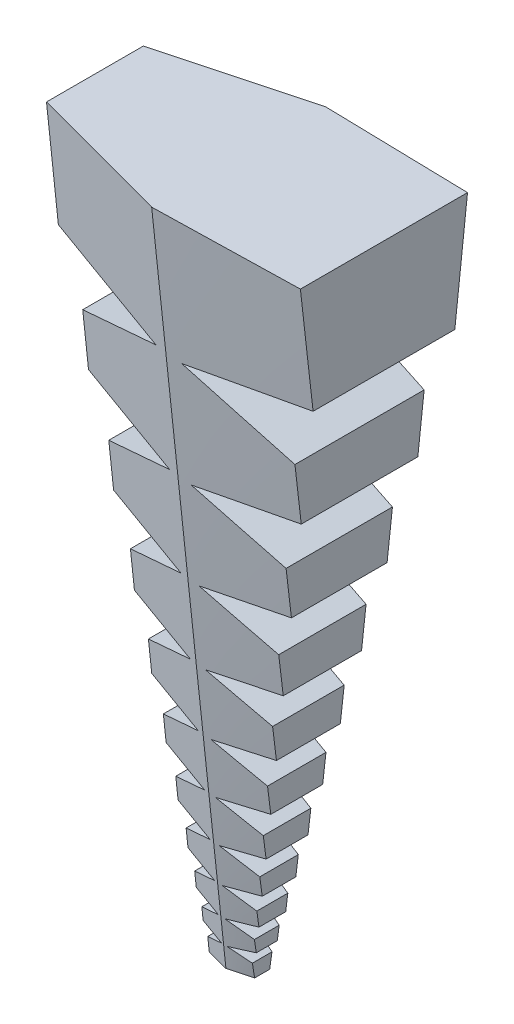
SolidWorks part; units mm, degrees
ref_plane "Front Plane" through (0, 0, 0) normal (0, 0, 1) x (1, 0, 0)
ref_plane "Top Plane" through (0, 0, 0) normal (0, 1, 0) x (1, 0, 0)
ref_plane "Right Plane" through (0, 0, 0) normal (1, 0, 0) x (0, 0, -1)
sketch "spiral_flat" plane through (0, 0, 0) normal (0, 0, 1) x (1, 0, 0)
  line L0 (3.2655, 0) -> (-3.2655, 0) construction
  line L1 (3.9293, 3.054) -> (-3.9293, 3.054) construction
  line L2 (4.728, 6.7288) -> (-4.728, 6.7288) construction
  line L3 (5.689, 11.1506) -> (-5.689, 11.1506) construction
  line L4 (6.8455, 16.4712) -> (-6.8455, 16.4712) construction
  line L5 (8.2369, 22.8733) -> (-8.2369, 22.8733) construction
  line L6 (9.9112, 30.5768) -> (-9.9112, 30.5768) construction
  line L7 (11.9259, 39.8461) -> (-11.9259, 39.8461) construction
  line L8 (14.35, 50.9996) -> (-14.35, 50.9996) construction
  line L9 (17.2669, 64.4202) -> (-17.2669, 64.4202) construction
  line L10 (20.7767, 80.5689) -> (-20.7767, 80.5689) construction
  line L11 (25, 100) -> (-25, 100) construction
  line L12 (0, -2.9617) -> (0, 103.8438) construction
  line L13 (3.2655, 0) -> (25, 100) construction
  line L14 (-3.2655, 0) -> (-25, 100) construction
  line L15 (0.3266, 0) -> (2.5, 100) construction
  line L16 (-0.3266, 0) -> (-2.5, 100) construction
  line L17 (-20.7767, 80.5689) -> (-20.7767, 100) construction
  line L18 (-17.2669, 64.4202) -> (-17.2669, 80.5689) construction
  line L19 (-14.35, 50.9996) -> (-14.35, 64.4202) construction
  line L20 (-11.9259, 39.8461) -> (-11.9259, 50.9996) construction
  line L21 (-9.9112, 30.5768) -> (-9.9112, 39.8461) construction
  line L22 (-8.2369, 22.8733) -> (-8.2369, 30.5768) construction
  line L23 (-6.8455, 16.4712) -> (-6.8455, 22.8733) construction
  line L24 (-5.689, 11.1506) -> (-5.689, 16.4712) construction
  line L25 (-4.728, 6.7288) -> (-4.728, 11.1506) construction
  line L26 (-3.9293, 3.054) -> (-3.9293, 6.7288) construction
  line L27 (-3.2655, 0) -> (-3.2655, 3.054) construction
  line L28 (20.7767, 80.5689) -> (20.7767, 100) construction
  line L29 (14.35, 50.9996) -> (14.35, 64.4202) construction
  line L30 (17.2669, 64.4202) -> (17.2669, 80.5689) construction
  line L31 (11.9259, 39.8461) -> (11.9259, 50.9996) construction
  line L32 (9.9112, 30.5768) -> (9.9112, 39.8461) construction
  line L33 (8.2369, 22.8733) -> (8.2369, 30.5768) construction
  line L34 (6.8455, 16.4712) -> (6.8455, 22.8733) construction
  line L35 (5.689, 11.1506) -> (5.689, 16.4712) construction
  line L36 (4.728, 6.7288) -> (4.728, 11.1506) construction
  line L37 (3.9293, 3.054) -> (3.9293, 6.7288) construction
  line L38 (3.2655, 0) -> (3.2655, 3.054) construction
  line L39 (-2.0777, 80.5689) -> (-17.2669, 75.0404) construction
  line L40 (-1.7267, 64.4202) -> (-17.2669, 67.1604) construction
  line L41 (-2.0777, 80.5689) -> (-20.7767, 83.866) construction
  line L42 (-1.7267, 64.4202) -> (-14.35, 59.8257) construction
  line L43 (-1.435, 50.9996) -> (-14.35, 53.2769) construction
  line L44 (-1.435, 50.9996) -> (-11.9259, 47.1812) construction
  line L45 (-1.1926, 39.8461) -> (-11.9259, 41.7387) construction
  line L46 (-1.1926, 39.8461) -> (-9.9112, 36.6728) construction
  line L47 (-0.9911, 30.5768) -> (-9.9112, 32.1496) construction
  line L48 (-0.9911, 30.5768) -> (-8.2369, 27.9395) construction
  line L49 (-0.8237, 22.8733) -> (-8.2369, 24.1805) construction
  line L50 (-0.8237, 22.8733) -> (-6.8455, 20.6816) construction
  line L51 (-0.6845, 16.4712) -> (-6.8455, 17.5576) construction
  line L52 (-0.6845, 16.4712) -> (-5.689, 14.6497) construction
  line L53 (-0.5689, 11.1506) -> (-5.689, 12.0534) construction
  line L54 (-0.5689, 11.1506) -> (-4.728, 9.6368) construction
  line L55 (-0.4728, 6.7288) -> (-4.728, 7.4791) construction
  line L56 (-0.4728, 6.7288) -> (-3.9293, 5.4708) construction
  line L57 (-0.3929, 3.054) -> (-3.9293, 3.6776) construction
  line L58 (-0.3929, 3.054) -> (-3.2655, 2.0085) construction
  line L59 (0.3929, 3.054) -> (3.2655, 2.0085) construction
  line L60 (0.3929, 3.054) -> (3.9293, 3.6776) construction
  line L61 (0.4728, 6.7288) -> (3.9293, 5.4708) construction
  line L62 (0.4728, 6.7288) -> (4.728, 7.4791) construction
  line L63 (0.5689, 11.1506) -> (4.728, 9.6368) construction
  line L64 (0.5689, 11.1506) -> (5.689, 12.0534) construction
  line L65 (0.6845, 16.4712) -> (5.689, 14.6497) construction
  line L66 (0.6845, 16.4712) -> (6.8455, 17.5576) construction
  line L67 (0.8237, 22.8733) -> (6.8455, 20.6816) construction
  line L68 (0.8237, 22.8733) -> (8.2369, 24.1805) construction
  line L69 (0.9911, 30.5768) -> (8.2369, 27.9395) construction
  line L70 (0.9911, 30.5768) -> (9.9112, 32.1496) construction
  line L71 (1.1926, 39.8461) -> (9.9112, 36.6728) construction
  line L72 (1.1926, 39.8461) -> (11.9259, 41.7387) construction
  line L73 (1.435, 50.9996) -> (11.9259, 47.1812) construction
  line L74 (1.435, 50.9996) -> (14.35, 53.2769) construction
  line L75 (1.7267, 64.4202) -> (14.35, 59.8257) construction
  line L76 (1.7267, 64.4202) -> (17.2669, 67.1604) construction
  line L77 (2.0777, 80.5689) -> (17.2669, 75.0404) construction
  line L78 (2.0777, 80.5689) -> (20.7767, 83.866) construction
  line L143 (-20.7767, 100) -> (-25, 100)
  line L144 (-25, 100) -> (-3.2655, 0)
  line L145 (-3.2655, 0) -> (-3.2655, 2.0085)
  line L146 (-0.3929, 3.054) -> (-3.9293, 3.6776)
  line L147 (-3.9293, 5.4708) -> (-0.4728, 6.7288)
  line L148 (-4.728, 7.4791) -> (-4.728, 9.6368)
  line L149 (-0.5689, 11.1506) -> (-5.689, 12.0534)
  line L150 (-5.689, 14.6497) -> (-0.6845, 16.4712)
  line L151 (-6.8455, 17.5576) -> (-6.8455, 20.6816)
  line L152 (-0.8237, 22.8733) -> (-8.2369, 24.1805)
  line L153 (-9.9112, 36.6728) -> (-1.1926, 39.8461)
  line L154 (-1.1926, 39.8461) -> (-11.9259, 41.7387)
  line L155 (-14.35, 59.8257) -> (-1.7267, 64.4202)
  line L156 (-1.7267, 64.4202) -> (-17.2669, 67.1604)
  line L157 (-17.2669, 75.0404) -> (-2.0777, 80.5689)
  line L158 (-20.7767, 83.866) -> (-20.7767, 100)
  line L159 (3.2655, 2.0085) -> (3.2655, 0)
  line L160 (0.3929, 3.054) -> (3.2655, 2.0085)
  line L161 (3.9293, 3.6776) -> (0.3929, 3.054)
  line L162 (3.9293, 5.4708) -> (3.9293, 3.6776)
  line L163 (0.4728, 6.7288) -> (3.9293, 5.4708)
  line L164 (4.728, 7.4791) -> (0.4728, 6.7288)
  line L165 (4.728, 9.6368) -> (4.728, 7.4791)
  line L166 (0.5689, 11.1506) -> (4.728, 9.6368)
  line L167 (5.689, 12.0534) -> (0.5689, 11.1506)
  line L168 (5.689, 14.6497) -> (5.689, 12.0534)
  line L169 (0.6845, 16.4712) -> (5.689, 14.6497)
  line L170 (6.8455, 17.5576) -> (0.6845, 16.4712)
  line L171 (6.8455, 20.6816) -> (6.8455, 17.5576)
  line L172 (0.8237, 22.8733) -> (6.8455, 20.6816)
  line L173 (8.2369, 24.1805) -> (0.8237, 22.8733)
  line L174 (8.2369, 27.9395) -> (8.2369, 24.1805)
  line L175 (0.9911, 30.5768) -> (8.2369, 27.9395)
  line L176 (9.9112, 32.1496) -> (0.9911, 30.5768)
  line L177 (9.9112, 36.6728) -> (9.9112, 32.1496)
  line L178 (1.1926, 39.8461) -> (9.9112, 36.6728)
  line L179 (11.9259, 41.7387) -> (1.1926, 39.8461)
  line L180 (11.9259, 47.1812) -> (11.9259, 41.7387)
  line L181 (1.435, 50.9996) -> (11.9259, 47.1812)
  line L182 (14.35, 53.2769) -> (1.435, 50.9996)
  line L183 (14.35, 59.8257) -> (14.35, 53.2769)
  line L184 (1.7267, 64.4202) -> (14.35, 59.8257)
  line L185 (17.2669, 67.1604) -> (1.7267, 64.4202)
  line L186 (17.2669, 75.0404) -> (17.2669, 67.1604)
  line L187 (2.0777, 80.5689) -> (17.2669, 75.0404)
  line L188 (20.7767, 83.866) -> (2.0777, 80.5689)
  line L189 (20.7767, 100) -> (20.7767, 83.866)
  line L190 (25, 100) -> (3.2655, 0)
  line L191 (20.7767, 100) -> (25, 100)
  line L192 (-20.7767, 83.866) -> (-2.0777, 80.5689)
  line L193 (-17.2669, 75.0404) -> (-17.2669, 67.1604)
  line L194 (-14.35, 59.8257) -> (-14.35, 53.2769)
  line L195 (-14.35, 53.2769) -> (-1.435, 50.9996)
  line L196 (-1.435, 50.9996) -> (-11.9259, 47.1812)
  line L197 (-11.9259, 47.1812) -> (-11.9259, 41.7387)
  line L198 (-9.9112, 36.6728) -> (-9.9112, 32.1496)
  line L199 (-9.9112, 32.1496) -> (-0.9911, 30.5768)
  line L200 (-0.9911, 30.5768) -> (-8.2369, 27.9395)
  line L201 (-8.2369, 27.9395) -> (-8.2369, 24.1805)
  line L202 (-6.8455, 20.6816) -> (-0.8237, 22.8733)
  line L203 (-6.8455, 17.5576) -> (-0.6845, 16.4712)
  line L204 (-5.689, 14.6497) -> (-5.689, 12.0534)
  line L205 (-0.5689, 11.1506) -> (-4.728, 9.6368)
  line L206 (-4.728, 7.4791) -> (-0.4728, 6.7288)
  line L207 (-3.9293, 5.4708) -> (-3.9293, 3.6776)
  line L208 (-0.3929, 3.054) -> (-3.2655, 2.0085)
  spline S0 degree 3 poles (0, 0) (0, 1.018) (0, 3.261) (0, 6.9778) (0, 11.4502) (0, 16.8317) (0, 23.3071) (0, 31.0987) (0, 40.4742) (0, 51.7553) (0, 65.3296) (0, 81.663) (0, 93.523) (0, 100) knots 0 0 0 0 0.03054 0.067288 0.111506 0.164712 0.228733 0.305768 0.398461 0.509996 0.644202 0.805689 1 1 1 1
  point P39 (0, 3.054)
  point P40 (0, 6.7288)
  point P41 (0, 11.1506)
  point P42 (0, 16.4712)
  point P43 (0, 22.8733)
  point P44 (0, 30.5768)
  point P45 (0, 39.8461)
  point P46 (0, 50.9996)
  point P47 (0, 64.4202)
  point P48 (0, 80.5689)
  point P49 (-0.3266, 0)
  point P50 (-0.3929, 3.054)
  point P51 (-0.4728, 6.7288)
  point P52 (-0.5689, 11.1506)
  point P53 (-0.6845, 16.4712)
  point P54 (-0.8237, 22.8733)
  point P55 (-0.9911, 30.5768)
  point P56 (-1.1926, 39.8461)
  point P57 (-1.435, 50.9996)
  point P58 (-1.7267, 64.4202)
  point P59 (-2.0777, 80.5689)
  point P60 (-2.5, 100)
  point P61 (0.3266, 0)
  point P62 (0.3929, 3.054)
  point P63 (0.4728, 6.7288)
  point P64 (0.5689, 11.1506)
  point P65 (0.6845, 16.4712)
  point P66 (0.8237, 22.8733)
  point P67 (0.9911, 30.5768)
  point P68 (1.1926, 39.8461)
  point P69 (1.435, 50.9996)
  point P70 (1.7267, 64.4202)
  point P71 (2.0777, 80.5689)
  point P72 (2.5, 100)
  dimension "D1" = 100
  dimension "D3" = 7.8586
  dimension "D2" = 6.531
  dimension "D4" = 9.456
  dimension "D5" = 11.3781
  dimension "D6" = 13.6909
  dimension "D7" = 16.4738
  dimension "D8" = 19.8224
  dimension "D9" = 23.8517
  dimension "D10" = 28.7
  dimension "D11" = 34.5338
  dimension "D12" = 41.5535
  dimension "D13" = 50
  dimension "D14" = 0.6531
  dimension "D15" = 0.7859
  dimension "D16" = 0.9456
  dimension "D17" = 1.1378
  dimension "D18" = 1.3691
  dimension "D19" = 1.6474
  dimension "D20" = 1.9822
  dimension "D21" = 2.3852
  dimension "D22" = 2.87
  dimension "D23" = 3.4534
  dimension "D24" = 4.1553
  dimension "D25" = 5
  dimension "D26" = 20
  dimension "D27" = 10
  dimension "D28" = 10
  dimension "D29" = 20
  dimension "D30" = 10
  dimension "D31" = 20
  dimension "D32" = 10
  dimension "D33" = 20
  dimension "D34" = 10
  dimension "D35" = 20
  dimension "D36" = 10
  dimension "D37" = 20
  dimension "D38" = 10
  dimension "D39" = 20
  dimension "D40" = 10
  dimension "D41" = 20
  dimension "D42" = 10
  dimension "D43" = 20
  dimension "D44" = 10
  dimension "D45" = 20
sketch "Sketch2" plane through (0, 0, 0) normal (0, 1, 0) x (1, 0, 0)
  line L0 (3.2655, 0) -> (-3.2384, 0) construction
  line L1 (0.0136, -1.9593) -> (0.0136, 1.9593) construction
  line L2 (3.2655, -1.9593) -> (3.2655, 1.9593) construction
  line L3 (-3.2384, -1.9593) -> (-3.2384, 1.9593) construction
  line L4 (3.2655, 1.9593) -> (-3.2384, 1.9593) construction
  line L5 (0.0136, 1.9593) -> (3.2655, 1.088) construction
  line L6 (3.2655, -1.9593) -> (-3.2384, -1.9593) construction
  line L7 (0.0136, -1.9593) -> (3.2655, -1.088) construction
  line L8 (0.0136, -1.9593) -> (-3.2384, -1.088) construction
  line L9 (0.0136, 1.9593) -> (-3.2384, 1.088) construction
  line L10 (0.0136, 1.9593) -> (-3.2384, 1.088)
  line L11 (-3.2384, 1.088) -> (-3.2384, -1.088)
  line L12 (-3.2384, -1.088) -> (0.0136, -1.9593)
  line L13 (0.0136, -1.9593) -> (3.2655, -1.088)
  line L14 (3.2655, -1.088) -> (3.2655, 1.088)
  line L15 (3.2655, 1.088) -> (0.0136, 1.9593)
  point P7 (0.0136, 0)
  dimension "D1" = 3.9186
  dimension "D2" = 15
ref_plane "Plane1" through (0, 100, 0) normal (0, 1, 0) x (1, 0, 0)
sketch "Sketch3" plane through (0, 100, 0) normal (0, 1, 0) x (1, 0, 0)
  line L2 (-0.1234, -12.5) -> (-0.1234, 12.5) construction
  line L6 (-0.1234, 12.5) -> (-25, 5.8343) construction
  line L8 (-0.1234, -12.5) -> (-25, -5.8343) construction
  line L9 (-0.1234, -12.5) -> (24.7531, -5.8343) construction
  line L10 (-0.1234, 12.5) -> (24.7531, 5.8343) construction
  line L12 (-25, -12.5) -> (-25, 12.5) construction
  line L16 (-0.1234, 12.5) -> (-25, 5.8343)
  line L17 (-25, 5.8343) -> (-25, -5.8343)
  line L18 (-25, -5.8343) -> (-0.1234, -12.5)
  line L23 (0.0136, 0) -> (29.6147, 0) construction
  line L24 (24.7531, 11.9201) -> (24.7531, -11.9201)
  line L25 (-0.1234, 12.5) -> (24.7531, 11.9201)
  line L26 (-0.1234, -12.5) -> (24.7531, -11.9201)
  line L27 (3.2655, 0) -> (-3.2384, 0) construction
  point P8 (-0.1234, 0)
  point P10 (24.7531, 0)
  dimension "D1" = 25
  dimension "D2" = 23.8402
  dimension "D3" = 0.1234
loft "Loft1" add profiles "Sketch2", "Sketch3" connector at (3.2655, 0, -1.0879) connector at (24.7531, 100, -11.9201)
extrude "Cut-Extrude2" cut sketch "spiral_flat" against normal through all both and the other way through all contours L192 L157 L193 L156 L155 L194 L195 L196 L197 L154 L153 L198 L199 L200 L201 L152 L202 L151 L203 L150 L204 L149 L205 L148 L206 L147 L207 L146 L208 L145 L144 L143 L158 | L188 L187 L186 L185 L184 L183 L182 L181 L180 L179 L178 L177 L176 L175 L174 L173 L172 L171 L170 L169 L168 L167 L166 L165 L164 L163 L162 L161 L160 L159 L190 L191 L189
